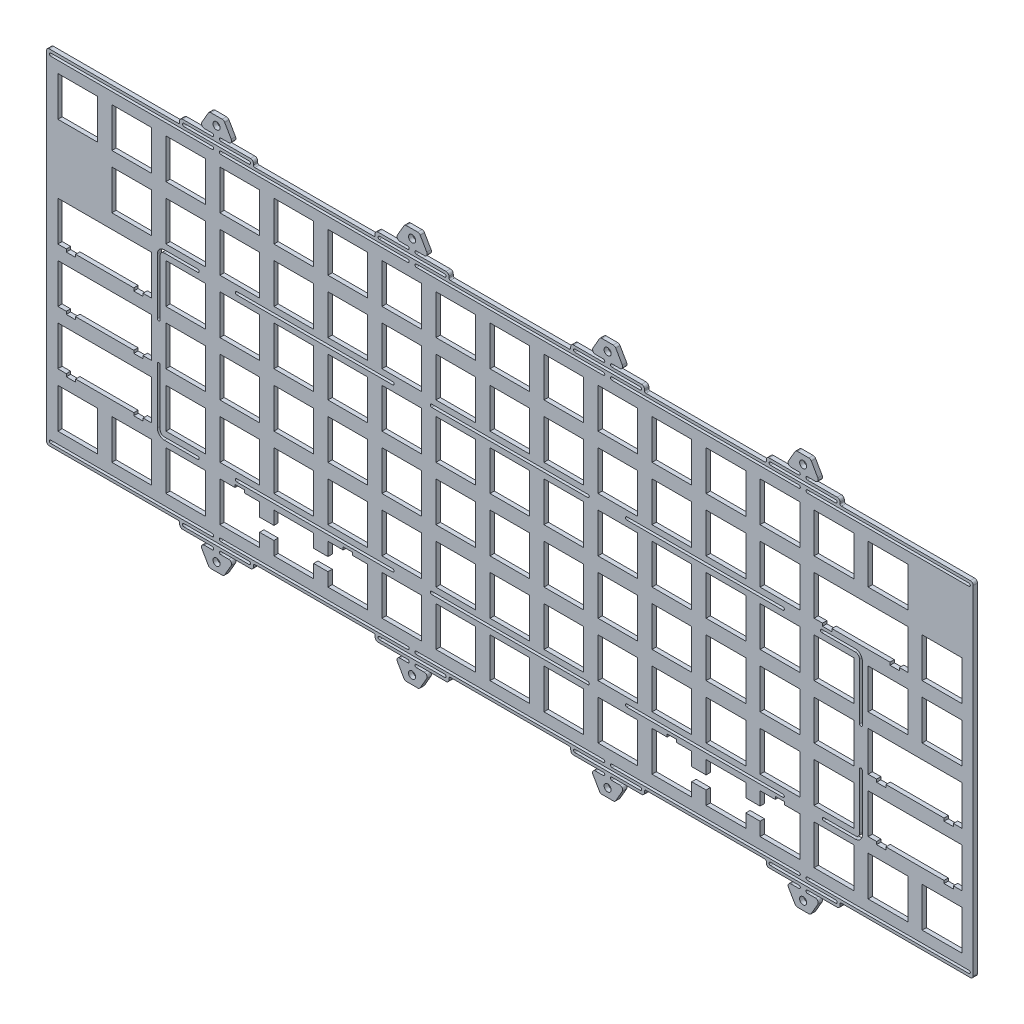
SolidWorks part; units mm, degrees
material "Acrylic (Medium-high impact)"
ref_plane "Front Plane" through (0, 0, 0) normal (0, 0, 1) x (1, 0, 0)
ref_plane "Top Plane" through (0, 0, 0) normal (0, 1, 0) x (1, 0, 0)
ref_plane "Right Plane" through (0, 0, 0) normal (1, 0, 0) x (0, 0, -1)
sketch "Sketch2" plane through (0, 0, 0) normal (0, 0, 1) x (1, 0, 0)
  line L0 (102.249, -54.6242) -> (102.249, -40.6233)
  line L1 (102.249, -40.6233) -> (96.9, -40.6233)
  line L2 (96.9, -40.6233) -> (96.9, -39.6546)
  line L3 (96.9, -39.6546) -> (93.6, -39.6546)
  line L4 (93.6, -39.6546) -> (93.6, -40.6233)
  line L5 (93.6, -40.6233) -> (88.25, -40.6233)
  line L6 (88.25, -40.6233) -> (88.25, -45.3238)
  line L7 (88.25, -45.3238) -> (83.199, -45.3238)
  line L8 (83.199, -45.3238) -> (83.199, -40.6233)
  line L9 (83.199, -40.6233) -> (69.2, -40.6233)
  line L10 (69.2, -40.6233) -> (69.2, -45.3238)
  line L11 (69.2, -45.3238) -> (64.149, -45.3238)
  line L12 (64.149, -45.3238) -> (64.149, -40.6233)
  line L13 (64.149, -40.6233) -> (58.801, -40.6233)
  line L14 (58.801, -40.6233) -> (58.801, -39.6546)
  line L15 (58.801, -39.6546) -> (55.5, -39.6546)
  line L16 (55.5, -39.6546) -> (55.5, -40.6233)
  line L17 (55.5, -40.6233) -> (50.15, -40.6233)
  line L18 (50.15, -40.6233) -> (50.15, -54.6242)
  line L19 (50.15, -54.6242) -> (64.149, -54.6242)
  line L20 (64.149, -54.6242) -> (64.149, -49.9223)
  line L21 (64.149, -49.9223) -> (69.2, -49.9223)
  line L22 (69.2, -49.9223) -> (69.2, -54.6242)
  line L23 (69.2, -54.6242) -> (83.199, -54.6242)
  line L24 (83.199, -54.6242) -> (83.199, -49.9223)
  line L25 (83.199, -49.9223) -> (88.25, -49.9223)
  line L26 (88.25, -49.9223) -> (88.25, -54.6242)
  line L27 (88.25, -54.6242) -> (102.249, -54.6242)
  line L28 (-50.1496, -54.6242) -> (-50.1496, -40.6233)
  line L29 (-50.1496, -40.6233) -> (-55.4991, -40.6233)
  line L30 (-55.4991, -40.6233) -> (-55.4991, -39.6546)
  line L31 (-55.4991, -39.6546) -> (-58.7994, -39.6546)
  line L32 (-58.7994, -39.6546) -> (-58.7994, -40.6233)
  line L33 (-58.7994, -40.6233) -> (-64.1503, -40.6233)
  line L34 (-64.1503, -40.6233) -> (-64.1503, -45.3238)
  line L35 (-64.1503, -45.3238) -> (-69.201, -45.3238)
  line L36 (-69.201, -45.3238) -> (-69.201, -40.6233)
  line L37 (-69.201, -40.6233) -> (-83.2003, -40.6233)
  line L38 (-83.2003, -40.6233) -> (-83.2003, -45.3238)
  line L39 (-83.2003, -45.3238) -> (-88.2496, -45.3238)
  line L40 (-88.2496, -45.3238) -> (-88.2496, -40.6233)
  line L41 (-88.2496, -40.6233) -> (-93.6003, -40.6233)
  line L42 (-93.6003, -40.6233) -> (-93.6003, -39.6546)
  line L43 (-93.6003, -39.6546) -> (-96.9003, -39.6546)
  line L44 (-96.9003, -39.6546) -> (-96.9003, -40.6233)
  line L45 (-96.9003, -40.6233) -> (-102.2503, -40.6233)
  line L46 (-102.2503, -40.6233) -> (-102.2503, -54.6242)
  line L47 (-102.2503, -54.6242) -> (-88.2496, -54.6242)
  line L48 (-88.2496, -54.6242) -> (-88.2496, -49.9223)
  line L49 (-88.2496, -49.9223) -> (-83.2003, -49.9223)
  line L50 (-83.2003, -49.9223) -> (-83.2003, -54.6242)
  line L51 (-83.2003, -54.6242) -> (-69.201, -54.6242)
  line L52 (-69.201, -54.6242) -> (-69.201, -49.9223)
  line L53 (-69.201, -49.9223) -> (-64.1503, -49.9223)
  line L54 (-64.1503, -49.9223) -> (-64.1503, -54.6242)
  line L55 (-64.1503, -54.6242) -> (-50.1496, -54.6242)
  line L56 (145.4, -40.6233) -> (159.399, -40.6233)
  line L57 (159.399, -40.6233) -> (159.399, -54.6242)
  line L58 (159.399, -54.6242) -> (145.4, -54.6242)
  line L59 (145.4, -54.6242) -> (145.4, -40.6233)
  line L60 (126.35, -40.6233) -> (140.349, -40.6233)
  line L61 (140.349, -40.6233) -> (140.349, -54.6242)
  line L62 (140.349, -54.6242) -> (126.35, -54.6242)
  line L63 (126.35, -54.6242) -> (126.35, -40.6233)
  line L64 (107.3, -40.6233) -> (121.299, -40.6233)
  line L65 (121.299, -40.6233) -> (121.299, -54.6242)
  line L66 (121.299, -54.6242) -> (107.3, -54.6242)
  line L67 (107.3, -54.6242) -> (107.3, -40.6233)
  line L68 (31.1, -40.6233) -> (45.099, -40.6233)
  line L69 (45.099, -40.6233) -> (45.099, -54.6242)
  line L70 (45.099, -54.6242) -> (31.1, -54.6242)
  line L71 (31.1, -54.6242) -> (31.1, -40.6233)
  line L72 (12.05, -40.6233) -> (26.049, -40.6233)
  line L73 (26.049, -40.6233) -> (26.049, -54.6242)
  line L74 (26.049, -54.6242) -> (12.05, -54.6242)
  line L75 (12.05, -54.6242) -> (12.05, -40.6233)
  line L76 (-7, -40.6233) -> (6.999, -40.6233)
  line L77 (6.999, -40.6233) -> (6.999, -54.6242)
  line L78 (6.999, -54.6242) -> (-7, -54.6242)
  line L79 (-7, -54.6242) -> (-7, -40.6233)
  line L80 (-26.05, -40.6233) -> (-12.051, -40.6233)
  line L81 (-12.051, -40.6233) -> (-12.051, -54.6242)
  line L82 (-12.051, -54.6242) -> (-26.05, -54.6242)
  line L83 (-26.05, -54.6242) -> (-26.05, -40.6233)
  line L84 (-45.102, -40.6233) -> (-31.101, -40.6233)
  line L85 (-31.101, -40.6233) -> (-31.101, -54.6242)
  line L86 (-31.101, -54.6242) -> (-45.102, -54.6242)
  line L87 (-45.102, -54.6242) -> (-45.102, -40.6233)
  line L88 (-121.3003, -40.6233) -> (-107.301, -40.6233)
  line L89 (-107.301, -40.6233) -> (-107.301, -54.6242)
  line L90 (-107.301, -54.6242) -> (-121.3003, -54.6242)
  line L91 (-121.3003, -54.6242) -> (-121.3003, -40.6233)
  line L92 (-140.3503, -40.6233) -> (-126.351, -40.6233)
  line L93 (-126.351, -40.6233) -> (-126.351, -54.6242)
  line L94 (-126.351, -54.6242) -> (-140.3503, -54.6242)
  line L95 (-140.3503, -54.6242) -> (-140.3503, -40.6233)
  line L96 (-159.4004, -40.6233) -> (-145.4008, -40.6233)
  line L97 (-145.4008, -40.6233) -> (-145.4008, -54.6242)
  line L98 (-145.4008, -54.6242) -> (-159.4004, -54.6242)
  line L99 (-159.4004, -54.6242) -> (-159.4004, -40.6233)
  line L100 (126.35, -21.5748) -> (126.35, -35.5742)
  line L101 (126.35, -35.5742) -> (129.325, -35.5742)
  line L102 (129.325, -35.5742) -> (129.325, -36.5443)
  line L103 (129.325, -36.5443) -> (132.624, -36.5443)
  line L104 (132.624, -36.5443) -> (132.624, -35.5742)
  line L105 (132.624, -35.5742) -> (153.125, -35.5742)
  line L106 (153.125, -35.5742) -> (153.125, -36.5443)
  line L107 (153.125, -36.5443) -> (156.424, -36.5443)
  line L108 (156.424, -36.5443) -> (156.424, -35.5742)
  line L109 (156.424, -35.5742) -> (159.399, -35.5742)
  line L110 (159.399, -35.5742) -> (159.399, -21.5748)
  line L111 (159.399, -21.5748) -> (126.35, -21.5748)
  line L112 (-159.4004, -21.5748) -> (-159.4004, -35.5742)
  line L113 (-159.4004, -35.5742) -> (-156.4252, -35.5742)
  line L114 (-156.4252, -35.5742) -> (-156.4252, -36.5443)
  line L115 (-156.4252, -36.5443) -> (-153.1262, -36.5443)
  line L116 (-153.1262, -36.5443) -> (-153.1262, -35.5742)
  line L117 (-153.1262, -35.5742) -> (-132.6251, -35.5742)
  line L118 (-132.6251, -35.5742) -> (-132.6251, -36.5443)
  line L119 (-132.6251, -36.5443) -> (-129.326, -36.5443)
  line L120 (-129.326, -36.5443) -> (-129.326, -35.5742)
  line L121 (-129.326, -35.5742) -> (-126.351, -35.5742)
  line L122 (-126.351, -35.5742) -> (-126.351, -21.5748)
  line L123 (-126.351, -21.5748) -> (-159.4004, -21.5748)
  line L124 (107.3, -21.5748) -> (121.299, -21.5748)
  line L125 (121.299, -21.5748) -> (121.299, -35.5742)
  line L126 (121.299, -35.5742) -> (107.3, -35.5742)
  line L127 (107.3, -35.5742) -> (107.3, -21.5748)
  line L128 (88.25, -21.5748) -> (102.249, -21.5748)
  line L129 (102.249, -21.5748) -> (102.249, -35.5742)
  line L130 (102.249, -35.5742) -> (88.25, -35.5742)
  line L131 (88.25, -35.5742) -> (88.25, -21.5748)
  line L132 (69.2, -21.5748) -> (83.199, -21.5748)
  line L133 (83.199, -21.5748) -> (83.199, -35.5742)
  line L134 (83.199, -35.5742) -> (69.2, -35.5742)
  line L135 (69.2, -35.5742) -> (69.2, -21.5748)
  line L136 (50.15, -21.5748) -> (64.149, -21.5748)
  line L137 (64.149, -21.5748) -> (64.149, -35.5742)
  line L138 (64.149, -35.5742) -> (50.15, -35.5742)
  line L139 (50.15, -35.5742) -> (50.15, -21.5748)
  line L140 (31.1, -21.5748) -> (45.099, -21.5748)
  line L141 (45.099, -21.5748) -> (45.099, -35.5742)
  line L142 (45.099, -35.5742) -> (31.1, -35.5742)
  line L143 (31.1, -35.5742) -> (31.1, -21.5748)
  line L144 (12.05, -21.5748) -> (26.049, -21.5748)
  line L145 (26.049, -21.5748) -> (26.049, -35.5742)
  line L146 (26.049, -35.5742) -> (12.05, -35.5742)
  line L147 (12.05, -35.5742) -> (12.05, -21.5748)
  line L148 (-7, -21.5748) -> (6.999, -21.5748)
  line L149 (6.999, -21.5748) -> (6.999, -35.5742)
  line L150 (6.999, -35.5742) -> (-7, -35.5742)
  line L151 (-7, -35.5742) -> (-7, -21.5748)
  line L152 (-26.05, -21.5748) -> (-12.051, -21.5748)
  line L153 (-12.051, -21.5748) -> (-12.051, -35.5742)
  line L154 (-12.051, -35.5742) -> (-26.05, -35.5742)
  line L155 (-26.05, -35.5742) -> (-26.05, -21.5748)
  line L156 (-45.102, -21.5748) -> (-31.101, -21.5748)
  line L157 (-31.101, -21.5748) -> (-31.101, -35.5742)
  line L158 (-31.101, -35.5742) -> (-45.102, -35.5742)
  line L159 (-45.102, -35.5742) -> (-45.102, -21.5748)
  line L160 (-64.1517, -21.5748) -> (-50.151, -21.5748)
  line L161 (-50.151, -21.5748) -> (-50.151, -35.5742)
  line L162 (-50.151, -35.5742) -> (-64.1517, -35.5742)
  line L163 (-64.1517, -35.5742) -> (-64.1517, -21.5748)
  line L164 (-83.2003, -21.5748) -> (-69.201, -21.5748)
  line L165 (-69.201, -21.5748) -> (-69.201, -35.5742)
  line L166 (-69.201, -35.5742) -> (-83.2003, -35.5742)
  line L167 (-83.2003, -35.5742) -> (-83.2003, -21.5748)
  line L168 (-102.2503, -21.5748) -> (-88.251, -21.5748)
  line L169 (-88.251, -21.5748) -> (-88.251, -35.5742)
  line L170 (-88.251, -35.5742) -> (-102.2503, -35.5742)
  line L171 (-102.2503, -35.5742) -> (-102.2503, -21.5748)
  line L172 (-121.3003, -21.5748) -> (-107.301, -21.5748)
  line L173 (-107.301, -21.5748) -> (-107.301, -35.5742)
  line L174 (-107.301, -35.5742) -> (-121.3003, -35.5742)
  line L175 (-121.3003, -35.5742) -> (-121.3003, -21.5748)
  line L176 (126.35, -2.5247) -> (126.35, -16.524)
  line L177 (126.35, -16.524) -> (129.325, -16.524)
  line L178 (129.325, -16.524) -> (129.325, -17.4942)
  line L179 (129.325, -17.4942) -> (132.624, -17.4942)
  line L180 (132.624, -17.4942) -> (132.624, -16.524)
  line L181 (132.624, -16.524) -> (153.125, -16.524)
  line L182 (153.125, -16.524) -> (153.125, -17.4942)
  line L183 (153.125, -17.4942) -> (156.424, -17.4942)
  line L184 (156.424, -17.4942) -> (156.424, -16.524)
  line L185 (156.424, -16.524) -> (159.399, -16.524)
  line L186 (159.399, -16.524) -> (159.399, -2.5247)
  line L187 (159.399, -2.5247) -> (126.35, -2.5247)
  line L188 (-159.4004, -2.5247) -> (-159.4004, -16.524)
  line L189 (-159.4004, -16.524) -> (-156.4252, -16.524)
  line L190 (-156.4252, -16.524) -> (-156.4252, -17.4942)
  line L191 (-156.4252, -17.4942) -> (-153.1262, -17.4942)
  line L192 (-153.1262, -17.4942) -> (-153.1262, -16.524)
  line L193 (-153.1262, -16.524) -> (-132.6251, -16.524)
  line L194 (-132.6251, -16.524) -> (-132.6251, -17.4942)
  line L195 (-132.6251, -17.4942) -> (-129.326, -17.4942)
  line L196 (-129.326, -17.4942) -> (-129.326, -16.524)
  line L197 (-129.326, -16.524) -> (-126.351, -16.524)
  line L198 (-126.351, -16.524) -> (-126.351, -2.5247)
  line L199 (-126.351, -2.5247) -> (-159.4004, -2.5247)
  line L200 (107.3, -2.5247) -> (121.299, -2.5247)
  line L201 (121.299, -2.5247) -> (121.299, -16.524)
  line L202 (121.299, -16.524) -> (107.3, -16.524)
  line L203 (107.3, -16.524) -> (107.3, -2.5247)
  line L204 (88.25, -2.5247) -> (102.249, -2.5247)
  line L205 (102.249, -2.5247) -> (102.249, -16.524)
  line L206 (102.249, -16.524) -> (88.25, -16.524)
  line L207 (88.25, -16.524) -> (88.25, -2.5247)
  line L208 (69.2, -2.5247) -> (83.199, -2.5247)
  line L209 (83.199, -2.5247) -> (83.199, -16.524)
  line L210 (83.199, -16.524) -> (69.2, -16.524)
  line L211 (69.2, -16.524) -> (69.2, -2.5247)
  line L212 (50.15, -2.5247) -> (64.149, -2.5247)
  line L213 (64.149, -2.5247) -> (64.149, -16.524)
  line L214 (64.149, -16.524) -> (50.15, -16.524)
  line L215 (50.15, -16.524) -> (50.15, -2.5247)
  line L216 (31.1, -2.5247) -> (45.099, -2.5247)
  line L217 (45.099, -2.5247) -> (45.099, -16.524)
  line L218 (45.099, -16.524) -> (31.1, -16.524)
  line L219 (31.1, -16.524) -> (31.1, -2.5247)
  line L220 (12.05, -2.5247) -> (26.049, -2.5247)
  line L221 (26.049, -2.5247) -> (26.049, -16.524)
  line L222 (26.049, -16.524) -> (12.05, -16.524)
  line L223 (12.05, -16.524) -> (12.05, -2.5247)
  line L224 (-7, -2.5247) -> (6.999, -2.5247)
  line L225 (6.999, -2.5247) -> (6.999, -16.524)
  line L226 (6.999, -16.524) -> (-7, -16.524)
  line L227 (-7, -16.524) -> (-7, -2.5247)
  line L228 (-26.05, -2.5247) -> (-12.051, -2.5247)
  line L229 (-12.051, -2.5247) -> (-12.051, -16.524)
  line L230 (-12.051, -16.524) -> (-26.05, -16.524)
  line L231 (-26.05, -16.524) -> (-26.05, -2.5247)
  line L232 (-45.102, -2.5247) -> (-31.101, -2.5247)
  line L233 (-31.101, -2.5247) -> (-31.101, -16.524)
  line L234 (-31.101, -16.524) -> (-45.102, -16.524)
  line L235 (-45.102, -16.524) -> (-45.102, -2.5247)
  line L236 (-64.1517, -2.5247) -> (-50.151, -2.5247)
  line L237 (-50.151, -2.5247) -> (-50.151, -16.524)
  line L238 (-50.151, -16.524) -> (-64.1517, -16.524)
  line L239 (-64.1517, -16.524) -> (-64.1517, -2.5247)
  line L240 (-83.2003, -2.5247) -> (-69.201, -2.5247)
  line L241 (-69.201, -2.5247) -> (-69.201, -16.524)
  line L242 (-69.201, -16.524) -> (-83.2003, -16.524)
  line L243 (-83.2003, -16.524) -> (-83.2003, -2.5247)
  line L244 (-102.2503, -2.5247) -> (-88.251, -2.5247)
  line L245 (-88.251, -2.5247) -> (-88.251, -16.524)
  line L246 (-88.251, -16.524) -> (-102.2503, -16.524)
  line L247 (-102.2503, -16.524) -> (-102.2503, -2.5247)
  line L248 (-121.3003, -2.5247) -> (-107.301, -2.5247)
  line L249 (-107.301, -2.5247) -> (-107.301, -16.524)
  line L250 (-107.301, -16.524) -> (-121.3003, -16.524)
  line L251 (-121.3003, -16.524) -> (-121.3003, -2.5247)
  line L252 (-159.4004, 16.5253) -> (-159.4004, 2.526)
  line L253 (-159.4004, 2.526) -> (-156.4252, 2.526)
  line L254 (-156.4252, 2.526) -> (-156.4252, 1.5558)
  line L255 (-156.4252, 1.5558) -> (-153.1262, 1.5558)
  line L256 (-153.1262, 1.5558) -> (-153.1262, 2.526)
  line L257 (-153.1262, 2.526) -> (-132.6251, 2.526)
  line L258 (-132.6251, 2.526) -> (-132.6251, 1.5558)
  line L259 (-132.6251, 1.5558) -> (-129.326, 1.5558)
  line L260 (-129.326, 1.5558) -> (-129.326, 2.526)
  line L261 (-129.326, 2.526) -> (-126.351, 2.526)
  line L262 (-126.351, 2.526) -> (-126.351, 16.5253)
  line L263 (-126.351, 16.5253) -> (-159.4004, 16.5253)
  line L264 (145.4, 16.5253) -> (159.399, 16.5253)
  line L265 (159.399, 16.5253) -> (159.399, 2.526)
  line L266 (159.399, 2.526) -> (145.4, 2.526)
  line L267 (145.4, 2.526) -> (145.4, 16.5253)
  line L268 (126.35, 16.5253) -> (140.349, 16.5253)
  line L269 (140.349, 16.5253) -> (140.349, 2.526)
  line L270 (140.349, 2.526) -> (126.35, 2.526)
  line L271 (126.35, 2.526) -> (126.35, 16.5253)
  line L272 (107.3, 16.5253) -> (121.299, 16.5253)
  line L273 (121.299, 16.5253) -> (121.299, 2.526)
  line L274 (121.299, 2.526) -> (107.3, 2.526)
  line L275 (107.3, 2.526) -> (107.3, 16.5253)
  line L276 (88.25, 16.5253) -> (102.249, 16.5253)
  line L277 (102.249, 16.5253) -> (102.249, 2.526)
  line L278 (102.249, 2.526) -> (88.25, 2.526)
  line L279 (88.25, 2.526) -> (88.25, 16.5253)
  line L280 (69.2, 16.5253) -> (83.199, 16.5253)
  line L281 (83.199, 16.5253) -> (83.199, 2.526)
  line L282 (83.199, 2.526) -> (69.2, 2.526)
  line L283 (69.2, 2.526) -> (69.2, 16.5253)
  line L284 (50.15, 16.5253) -> (64.149, 16.5253)
  line L285 (64.149, 16.5253) -> (64.149, 2.526)
  line L286 (64.149, 2.526) -> (50.15, 2.526)
  line L287 (50.15, 2.526) -> (50.15, 16.5253)
  line L288 (31.1, 16.5253) -> (45.099, 16.5253)
  line L289 (45.099, 16.5253) -> (45.099, 2.526)
  line L290 (45.099, 2.526) -> (31.1, 2.526)
  line L291 (31.1, 2.526) -> (31.1, 16.5253)
  line L292 (12.05, 16.5253) -> (26.049, 16.5253)
  line L293 (26.049, 16.5253) -> (26.049, 2.526)
  line L294 (26.049, 2.526) -> (12.05, 2.526)
  line L295 (12.05, 2.526) -> (12.05, 16.5253)
  line L296 (-7, 16.5253) -> (6.999, 16.5253)
  line L297 (6.999, 16.5253) -> (6.999, 2.526)
  line L298 (6.999, 2.526) -> (-7, 2.526)
  line L299 (-7, 2.526) -> (-7, 16.5253)
  line L300 (-26.05, 16.5253) -> (-12.051, 16.5253)
  line L301 (-12.051, 16.5253) -> (-12.051, 2.526)
  line L302 (-12.051, 2.526) -> (-26.05, 2.526)
  line L303 (-26.05, 2.526) -> (-26.05, 16.5253)
  line L304 (-45.102, 16.5253) -> (-31.101, 16.5253)
  line L305 (-31.101, 16.5253) -> (-31.101, 2.526)
  line L306 (-31.101, 2.526) -> (-45.102, 2.526)
  line L307 (-45.102, 2.526) -> (-45.102, 16.5253)
  line L308 (-64.1517, 16.5253) -> (-50.151, 16.5253)
  line L309 (-50.151, 16.5253) -> (-50.151, 2.526)
  line L310 (-50.151, 2.526) -> (-64.1517, 2.526)
  line L311 (-64.1517, 2.526) -> (-64.1517, 16.5253)
  line L312 (-83.2003, 16.5253) -> (-69.201, 16.5253)
  line L313 (-69.201, 16.5253) -> (-69.201, 2.526)
  line L314 (-69.201, 2.526) -> (-83.2003, 2.526)
  line L315 (-83.2003, 2.526) -> (-83.2003, 16.5253)
  line L316 (-102.2503, 16.5253) -> (-88.251, 16.5253)
  line L317 (-88.251, 16.5253) -> (-88.251, 2.526)
  line L318 (-88.251, 2.526) -> (-102.2503, 2.526)
  line L319 (-102.2503, 2.526) -> (-102.2503, 16.5253)
  line L320 (-121.3003, 16.5253) -> (-107.301, 16.5253)
  line L321 (-107.301, 16.5253) -> (-107.301, 2.526)
  line L322 (-107.301, 2.526) -> (-121.3003, 2.526)
  line L323 (-121.3003, 2.526) -> (-121.3003, 16.5253)
  line L324 (107.3, 35.5753) -> (107.3, 21.576)
  line L325 (107.3, 21.576) -> (110.275, 21.576)
  line L326 (110.275, 21.576) -> (110.275, 20.6058)
  line L327 (110.275, 20.6058) -> (113.574, 20.6058)
  line L328 (113.574, 20.6058) -> (113.574, 21.576)
  line L329 (113.574, 21.576) -> (134.075, 21.576)
  line L330 (134.075, 21.576) -> (134.075, 20.6058)
  line L331 (134.075, 20.6058) -> (137.374, 20.6058)
  line L332 (137.374, 20.6058) -> (137.374, 21.576)
  line L333 (137.374, 21.576) -> (140.349, 21.576)
  line L334 (140.349, 21.576) -> (140.349, 35.5753)
  line L335 (140.349, 35.5753) -> (107.3, 35.5753)
  line L336 (145.4, 35.5753) -> (159.399, 35.5753)
  line L337 (159.399, 35.5753) -> (159.399, 21.576)
  line L338 (159.399, 21.576) -> (145.4, 21.576)
  line L339 (145.4, 21.576) -> (145.4, 35.5753)
  line L340 (88.25, 35.5753) -> (102.249, 35.5753)
  line L341 (102.249, 35.5753) -> (102.249, 21.576)
  line L342 (102.249, 21.576) -> (88.25, 21.576)
  line L343 (88.25, 21.576) -> (88.25, 35.5753)
  line L344 (69.2, 35.5753) -> (83.199, 35.5753)
  line L345 (83.199, 35.5753) -> (83.199, 21.576)
  line L346 (83.199, 21.576) -> (69.2, 21.576)
  line L347 (69.2, 21.576) -> (69.2, 35.5753)
  line L348 (50.15, 35.5753) -> (64.149, 35.5753)
  line L349 (64.149, 35.5753) -> (64.149, 21.576)
  line L350 (64.149, 21.576) -> (50.15, 21.576)
  line L351 (50.15, 21.576) -> (50.15, 35.5753)
  line L352 (31.1, 35.5753) -> (45.099, 35.5753)
  line L353 (45.099, 35.5753) -> (45.099, 21.576)
  line L354 (45.099, 21.576) -> (31.1, 21.576)
  line L355 (31.1, 21.576) -> (31.1, 35.5753)
  line L356 (12.05, 35.5753) -> (26.049, 35.5753)
  line L357 (26.049, 35.5753) -> (26.049, 21.576)
  line L358 (26.049, 21.576) -> (12.05, 21.576)
  line L359 (12.05, 21.576) -> (12.05, 35.5753)
  line L360 (-7, 35.5753) -> (6.999, 35.5753)
  line L361 (6.999, 35.5753) -> (6.999, 21.576)
  line L362 (6.999, 21.576) -> (-7, 21.576)
  line L363 (-7, 21.576) -> (-7, 35.5753)
  line L364 (-26.05, 35.5753) -> (-12.051, 35.5753)
  line L365 (-12.051, 35.5753) -> (-12.051, 21.576)
  line L366 (-12.051, 21.576) -> (-26.05, 21.576)
  line L367 (-26.05, 21.576) -> (-26.05, 35.5753)
  line L368 (-45.102, 35.5753) -> (-31.101, 35.5753)
  line L369 (-31.101, 35.5753) -> (-31.101, 21.576)
  line L370 (-31.101, 21.576) -> (-45.102, 21.576)
  line L371 (-45.102, 21.576) -> (-45.102, 35.5753)
  line L372 (-64.1517, 35.5753) -> (-50.151, 35.5753)
  line L373 (-50.151, 35.5753) -> (-50.151, 21.576)
  line L374 (-50.151, 21.576) -> (-64.1517, 21.576)
  line L375 (-64.1517, 21.576) -> (-64.1517, 35.5753)
  line L376 (-83.2003, 35.5753) -> (-69.201, 35.5753)
  line L377 (-69.201, 35.5753) -> (-69.201, 21.576)
  line L378 (-69.201, 21.576) -> (-83.2003, 21.576)
  line L379 (-83.2003, 21.576) -> (-83.2003, 35.5753)
  line L380 (-102.2503, 35.5753) -> (-88.251, 35.5753)
  line L381 (-88.251, 35.5753) -> (-88.251, 21.576)
  line L382 (-88.251, 21.576) -> (-102.2503, 21.576)
  line L383 (-102.2503, 21.576) -> (-102.2503, 35.5753)
  line L384 (-121.3003, 35.5753) -> (-107.301, 35.5753)
  line L385 (-107.301, 35.5753) -> (-107.301, 21.576)
  line L386 (-107.301, 21.576) -> (-121.3003, 21.576)
  line L387 (-121.3003, 21.576) -> (-121.3003, 35.5753)
  line L388 (-140.3503, 35.5753) -> (-126.351, 35.5753)
  line L389 (-126.351, 35.5753) -> (-126.351, 21.576)
  line L390 (-126.351, 21.576) -> (-140.3503, 21.576)
  line L391 (-140.3503, 21.576) -> (-140.3503, 35.5753)
  line L392 (126.35, 54.6252) -> (140.349, 54.6252)
  line L393 (140.349, 54.6252) -> (140.349, 40.626)
  line L394 (140.349, 40.626) -> (126.35, 40.626)
  line L395 (126.35, 40.626) -> (126.35, 54.6252)
  line L396 (107.3, 54.6252) -> (121.299, 54.6252)
  line L397 (121.299, 54.6252) -> (121.299, 40.626)
  line L398 (121.299, 40.626) -> (107.3, 40.626)
  line L399 (107.3, 40.626) -> (107.3, 54.6252)
  line L400 (88.25, 54.6252) -> (102.249, 54.6252)
  line L401 (102.249, 54.6252) -> (102.249, 40.626)
  line L402 (102.249, 40.626) -> (88.25, 40.626)
  line L403 (88.25, 40.626) -> (88.25, 54.6252)
  line L404 (69.2, 54.6252) -> (83.199, 54.6252)
  line L405 (83.199, 54.6252) -> (83.199, 40.626)
  line L406 (83.199, 40.626) -> (69.2, 40.626)
  line L407 (69.2, 40.626) -> (69.2, 54.6252)
  line L408 (50.15, 54.6252) -> (64.149, 54.6252)
  line L409 (64.149, 54.6252) -> (64.149, 40.626)
  line L410 (64.149, 40.626) -> (50.15, 40.626)
  line L411 (50.15, 40.626) -> (50.15, 54.6252)
  line L412 (31.1, 54.6252) -> (45.099, 54.6252)
  line L413 (45.099, 54.6252) -> (45.099, 40.626)
  line L414 (45.099, 40.626) -> (31.1, 40.626)
  line L415 (31.1, 40.626) -> (31.1, 54.6252)
  line L416 (12.05, 54.6252) -> (26.049, 54.6252)
  line L417 (26.049, 54.6252) -> (26.049, 40.626)
  line L418 (26.049, 40.626) -> (12.05, 40.626)
  line L419 (12.05, 40.626) -> (12.05, 54.6252)
  line L420 (-7, 54.6252) -> (6.999, 54.6252)
  line L421 (6.999, 54.6252) -> (6.999, 40.626)
  line L422 (6.999, 40.626) -> (-7, 40.626)
  line L423 (-7, 40.626) -> (-7, 54.6252)
  line L424 (-26.05, 54.6252) -> (-12.051, 54.6252)
  line L425 (-12.051, 54.6252) -> (-12.051, 40.626)
  line L426 (-12.051, 40.626) -> (-26.05, 40.626)
  line L427 (-26.05, 40.626) -> (-26.05, 54.6252)
  line L428 (-45.102, 54.6252) -> (-31.101, 54.6252)
  line L429 (-31.101, 54.6252) -> (-31.101, 40.626)
  line L430 (-31.101, 40.626) -> (-45.102, 40.626)
  line L431 (-45.102, 40.626) -> (-45.102, 54.6252)
  line L432 (-64.1517, 54.6252) -> (-50.151, 54.6252)
  line L433 (-50.151, 54.6252) -> (-50.151, 40.626)
  line L434 (-50.151, 40.626) -> (-64.1517, 40.626)
  line L435 (-64.1517, 40.626) -> (-64.1517, 54.6252)
  line L436 (-83.2003, 54.6252) -> (-69.201, 54.6252)
  line L437 (-69.201, 54.6252) -> (-69.201, 40.626)
  line L438 (-69.201, 40.626) -> (-83.2003, 40.626)
  line L439 (-83.2003, 40.626) -> (-83.2003, 54.6252)
  line L440 (-102.2503, 54.6252) -> (-88.251, 54.6252)
  line L441 (-88.251, 54.6252) -> (-88.251, 40.626)
  line L442 (-88.251, 40.626) -> (-102.2503, 40.626)
  line L443 (-102.2503, 40.626) -> (-102.2503, 54.6252)
  line L444 (-121.3003, 54.6252) -> (-107.301, 54.6252)
  line L445 (-107.301, 54.6252) -> (-107.301, 40.626)
  line L446 (-107.301, 40.626) -> (-121.3003, 40.626)
  line L447 (-121.3003, 40.626) -> (-121.3003, 54.6252)
  line L448 (-140.3503, 54.6252) -> (-126.351, 54.6252)
  line L449 (-126.351, 54.6252) -> (-126.351, 40.626)
  line L450 (-126.351, 40.626) -> (-140.3503, 40.626)
  line L451 (-140.3503, 40.626) -> (-140.3503, 54.6252)
  line L452 (-159.4004, 54.6252) -> (-145.4008, 54.6252)
  line L453 (-145.4008, 54.6252) -> (-145.4008, 40.626)
  line L454 (-145.4008, 40.626) -> (-159.4004, 40.626)
  line L455 (-159.4004, 40.626) -> (-159.4004, 54.6252)
  line L456 (-162.4006, -55.6246) -> (-162.4006, 55.6256) construction
  line L457 (-160.4006, 57.6256) -> (160.3992, 57.6256) construction
  line L458 (162.3992, 55.6256) -> (162.3992, -55.6246) construction
  line L459 (160.3992, -57.6246) -> (-160.4006, -57.6246) construction
  line L461 (-172.4004, 69.6252) -> (172.399, 69.6252)
  line L462 (-172.4004, 69.6252) -> (-172.4004, -69.6242)
  line L463 (-172.4004, -69.6242) -> (172.399, -69.6242)
  line L464 (172.399, 69.6252) -> (172.399, -69.6242)
  circle A0 centre (-152.4006, 47.6256) radius 2 construction
  circle A1 centre (-133.3508, 47.6256) radius 2 construction
  circle A2 centre (-114.3008, 47.6256) radius 2 construction
  circle A3 centre (-95.2508, 47.6256) radius 2 construction
  circle A4 centre (-76.2008, 47.6256) radius 2 construction
  circle A5 centre (-57.1508, 47.6256) radius 2 construction
  circle A6 centre (-38.1008, 47.6256) radius 2 construction
  circle A7 centre (-19.0508, 47.6256) radius 2 construction
  circle A8 centre (-0.0008, 47.6256) radius 2 construction
  circle A9 centre (19.0492, 47.6256) radius 2 construction
  circle A10 centre (38.0992, 47.6256) radius 2 construction
  circle A11 centre (57.1492, 47.6256) radius 2 construction
  circle A12 centre (76.1992, 47.6256) radius 2 construction
  circle A13 centre (95.2492, 47.6256) radius 2 construction
  circle A14 centre (114.2992, 47.6256) radius 2 construction
  circle A15 centre (133.3492, 47.6256) radius 2 construction
  circle A16 centre (152.3992, 28.5756) radius 2 construction
  circle A17 centre (133.3492, 28.5756) radius 2 construction
  circle A18 centre (95.2492, 28.5756) radius 2 construction
  circle A19 centre (152.3992, 9.5256) radius 2 construction
  circle A20 centre (133.3492, 9.5256) radius 2 construction
  circle A21 centre (114.2992, 9.5256) radius 2 construction
  circle A22 centre (95.2492, 9.5256) radius 2 construction
  circle A23 centre (76.1992, 9.5256) radius 2 construction
  circle A24 centre (76.1992, 28.5756) radius 2 construction
  circle A25 centre (57.1492, 28.5756) radius 2 construction
  circle A26 centre (57.1492, 9.5256) radius 2 construction
  circle A27 centre (38.0992, 28.5756) radius 2 construction
  circle A28 centre (19.0492, 28.5756) radius 2 construction
  circle A29 centre (-0.0008, 28.5756) radius 2 construction
  circle A30 centre (-19.0508, 28.5756) radius 2 construction
  circle A31 centre (-38.1008, 28.5756) radius 2 construction
  circle A32 centre (-57.1508, 28.5756) radius 2 construction
  circle A33 centre (-76.2008, 28.5756) radius 2 construction
  circle A34 centre (-95.2508, 28.5756) radius 2 construction
  circle A35 centre (-114.3008, 28.5756) radius 2 construction
  circle A36 centre (-133.3508, 28.5756) radius 2 construction
  circle A37 centre (-133.3508, 9.5256) radius 2 construction
  circle A38 centre (-114.3008, 9.5256) radius 2 construction
  circle A39 centre (-133.3508, -9.5244) radius 2 construction
  circle A40 centre (-95.2508, 9.5256) radius 2 construction
  circle A41 centre (-76.2008, 9.5256) radius 2 construction
  circle A42 centre (-57.1508, 9.5256) radius 2 construction
  circle A43 centre (-38.1008, 9.5256) radius 2 construction
  circle A44 centre (-19.0508, 9.5256) radius 2 construction
  circle A45 centre (-0.0008, 9.5256) radius 2 construction
  circle A46 centre (19.0492, 9.5256) radius 2 construction
  circle A47 centre (38.0992, 9.5256) radius 2 construction
  circle A48 centre (152.3992, -9.5244) radius 2 construction
  circle A49 centre (152.3992, -28.5746) radius 2 construction
  circle A50 centre (152.3992, -47.6246) radius 2 construction
  circle A51 centre (133.3492, -47.6246) radius 2 construction
  circle A52 centre (114.2992, -47.6246) radius 2 construction
  circle A53 centre (95.2492, -47.6246) radius 2 construction
  circle A54 centre (114.2992, -28.5746) radius 2 construction
  circle A55 centre (95.2492, -28.5746) radius 2 construction
  circle A56 centre (76.1992, -47.6246) radius 2 construction
  circle A57 centre (57.1492, -47.6246) radius 2 construction
  circle A58 centre (57.1492, -28.5746) radius 2 construction
  circle A59 centre (57.1492, -9.5244) radius 2 construction
  circle A60 centre (76.1992, -9.5244) radius 2 construction
  circle A61 centre (76.1992, -28.5746) radius 2 construction
  circle A62 centre (95.2492, -9.5244) radius 2 construction
  circle A63 centre (114.2992, -9.5244) radius 2 construction
  circle A64 centre (38.0992, -9.5244) radius 2 construction
  circle A65 centre (38.0992, -28.5746) radius 2 construction
  circle A66 centre (38.0992, -47.6246) radius 2 construction
  circle A67 centre (19.0492, -28.5746) radius 2 construction
  circle A68 centre (19.0492, -9.5244) radius 2 construction
  circle A69 centre (19.0492, -47.6246) radius 2 construction
  circle A70 centre (-0.0008, -9.5244) radius 2 construction
  circle A71 centre (-19.0508, -9.5244) radius 2 construction
  circle A72 centre (-19.0508, -28.5746) radius 2 construction
  circle A73 centre (-0.0008, -28.5746) radius 2 construction
  circle A74 centre (-0.0008, -47.6246) radius 2 construction
  circle A75 centre (-19.0508, -47.6246) radius 2 construction
  circle A76 centre (-38.1008, -28.5746) radius 2 construction
  circle A77 centre (-38.1008, -9.5244) radius 2 construction
  circle A78 centre (-57.1508, -9.5244) radius 2 construction
  circle A79 centre (-38.1008, -47.6246) radius 2 construction
  circle A80 centre (-57.1494, -47.6246) radius 2 construction
  circle A81 centre (-57.1508, -28.5746) radius 2 construction
  circle A82 centre (-76.2008, -47.6246) radius 2 construction
  circle A83 centre (-76.2008, -28.5746) radius 2 construction
  circle A84 centre (-76.2008, -9.5244) radius 2 construction
  circle A85 centre (-95.2508, -9.5244) radius 2 construction
  circle A86 centre (-95.2508, -28.5746) radius 2 construction
  circle A87 centre (-95.2508, -47.6246) radius 2 construction
  circle A88 centre (-114.3008, -47.6246) radius 2 construction
  circle A89 centre (-114.3008, -28.5746) radius 2 construction
  circle A90 centre (-114.3008, -9.5244) radius 2 construction
  circle A91 centre (-133.3508, -28.5746) radius 2 construction
  circle A92 centre (-133.3508, -47.6246) radius 2 construction
  circle A93 centre (-152.4006, -47.6246) radius 2 construction
  circle A94 centre (-152.4006, 9.5256) radius 2 construction
  circle A95 centre (-152.4006, -9.5244) radius 2 construction
  circle A96 centre (-152.4006, -28.5746) radius 2 construction
  circle A97 centre (133.3497, -28.5746) radius 2 construction
  circle A98 centre (133.3497, -9.5244) radius 2 construction
  circle A99 centre (114.2997, 28.5756) radius 2 construction
  circle A100 centre (-142.8757, 9.5257) radius 2 construction
  circle A101 centre (-142.8757, -9.5243) radius 2 construction
  circle A102 centre (-142.8757, -28.5744) radius 2 construction
  circle A103 centre (142.8745, -28.5744) radius 2 construction
  circle A104 centre (142.8745, -9.5243) radius 2 construction
  circle A105 centre (123.8245, 28.5757) radius 2 construction
  arc A106 (-160.4006, 57.6256) -> (-162.4006, 55.6256) centre (-160.4006, 55.6256) ccw construction
  arc A107 (162.3992, 55.6256) -> (160.3992, 57.6256) centre (160.3992, 55.6256) ccw construction
  arc A108 (160.3992, -57.6246) -> (162.3992, -55.6246) centre (160.3992, -55.6246) ccw construction
  arc A109 (-162.4006, -55.6246) -> (-160.4006, -57.6246) centre (-160.4006, -55.6246) ccw construction
  point P680 (0, 0)
  dimension "D1" = 4
  dimension "D2" = 6.999
  dimension "D3" = 12.05
  dimension "D4" = 19.0492
  dimension "D5" = 26.049
  dimension "D6" = 31.1
  dimension "D7" = 38.0992
  dimension "D8" = 50.15
  dimension "D9" = 55.5
  dimension "D10" = 57.1492
  dimension "D11" = 58.801
  dimension "D12" = 69.2
  dimension "D13" = 76.1992
  dimension "D14" = 95.2492
  dimension "D15" = 96.9
  dimension "D16" = 107.3
  dimension "D17" = 110.275
  dimension "D18" = 113.574
  dimension "D19" = 114.2992
  dimension "D20" = 114.2997
  dimension "D21" = 123.8245
  dimension "D22" = 133.3492
  dimension "D23" = 133.3497
  dimension "D24" = 134.075
  dimension "D25" = 142.8745
  dimension "D26" = 152.3992
  dimension "D27" = 162.3992
  dimension "D28" = 0.0008
  dimension "D29" = 12.051
  dimension "D30" = 19.0508
  dimension "D31" = 31.101
  dimension "D32" = 38.1008
  dimension "D33" = 45.102
  dimension "D34" = 50.1496
  dimension "D35" = 50.151
  dimension "D36" = 55.4991
  dimension "D37" = 57.1494
  dimension "D38" = 57.1508
  dimension "D39" = 58.7994
  dimension "D40" = 64.1503
  dimension "D41" = 69.201
  dimension "D42" = 76.2008
  dimension "D43" = 83.2003
  dimension "D44" = 88.2496
  dimension "D45" = 95.2508
  dimension "D46" = 107.301
  dimension "D47" = 114.3008
  dimension "D48" = 126.351
  dimension "D49" = 132.6251
  dimension "D50" = 133.3508
  dimension "D51" = 142.8757
  dimension "D52" = 145.4008
  dimension "D53" = 152.4006
  dimension "D54" = 153.1262
  dimension "D55" = 159.4004
  dimension "D56" = 162.4006
  dimension "D57" = 1.5558
  dimension "D58" = 2.526
  dimension "D59" = 9.5256
  dimension "D60" = 9.5257
  dimension "D61" = 20.6058
  dimension "D62" = 28.5756
  dimension "D63" = 28.5757
  dimension "D64" = 40.626
  dimension "D65" = 47.6256
  dimension "D66" = 54.6252
  dimension "D67" = 57.6256
  dimension "D68" = 2.5247
  dimension "D69" = 9.5243
  dimension "D70" = 9.5244
  dimension "D71" = 21.5748
  dimension "D72" = 28.5744
  dimension "D73" = 28.5746
  dimension "D74" = 35.5742
  dimension "D75" = 39.6546
  dimension "D76" = 40.6233
  dimension "D77" = 45.3238
  dimension "D78" = 47.6246
  dimension "D79" = 49.9223
  dimension "D80" = 54.6242
  dimension "D81" = 57.6246
  dimension "D82" = 0.9701
  dimension "D83" = 172.399
  dimension "D84" = 69.6242
  dimension "D86" = 172.4004
  dimension "D87" = 69.6252
extrude "Boss-Extrude1" add sketch "Sketch2" along normal blind 1.524
sketch "Sketch3" plane through (0, 0, 1.524) normal (0, 0, 1) x (1, 0, 0)
  line L0 (-172.4004, -69.6242) -> (172.399, -69.6242) construction
  line L1 (-172.4004, -69.6242) -> (-103.4405, -69.6242) construction
  line L2 (-114.9405, -61.6242) -> (-91.9405, -61.6242)
  line L3 (-34.4807, -69.6242) -> (34.4792, -69.6242) construction
  line L4 (34.4792, -69.6242) -> (103.4391, -69.6242) construction
  line L5 (103.4391, -69.6242) -> (172.399, -69.6242) construction
  line L6 (-103.4405, -69.6242) -> (-103.4405, 85.065) construction
  line L7 (-34.4807, -69.6242) -> (-34.4807, 85.065) construction
  line L8 (34.4792, -69.6242) -> (34.4792, 85.065) construction
  line L9 (103.4391, -69.6242) -> (103.4391, 85.065) construction
  line L10 (-114.9405, -60.6242) -> (-91.9405, -60.6242)
  line L11 (-106.3065, -69.1242) -> (-108.6159, -65.1242)
  line L12 (-107.7499, -63.6242) -> (-104.9405, -63.6242)
  line L13 (-104.9405, -62.6242) -> (-115.4405, -62.6242)
  line L14 (-116.4405, -61.6242) -> (-116.4405, -61.1242)
  line L15 (-116.9405, -60.6242) -> (-137.9205, -60.6242)
  line L16 (-103.4405, -69.6242) -> (-34.4807, -69.6242) construction
  line L17 (-103.4405, -55.7341) -> (-172.4004, -55.7341) construction
  line L18 (-172.4004, 69.6252) -> (-172.4004, -69.6242) construction
  line L19 (-137.9205, -55.7341) -> (-137.9205, -69.6242) construction
  line L20 (-116.4405, -60.6242) -> (-137.9205, -60.6242) construction
  line L21 (-34.4807, -56.8321) -> (34.4792, -56.8321) construction
  line L25 (-103.4405, -60.6242) -> (-103.4405, -61.6242) construction
  line L26 (-105.4405, -69.6242) -> (-101.4405, -69.6242)
  line L27 (-100.5745, -69.1242) -> (-98.2651, -65.1242)
  line L28 (-99.1311, -63.6242) -> (-101.9405, -63.6242)
  line L29 (-101.9405, -62.6242) -> (-91.4405, -62.6242)
  line L30 (-90.4405, -61.6242) -> (-90.4405, -61.1242)
  line L31 (-89.9405, -60.6242) -> (-68.9606, -60.6242)
  line L32 (-47.9806, -60.6242) -> (-68.9606, -60.6242)
  line L33 (-47.4807, -61.6242) -> (-47.4807, -61.1242)
  line L34 (-35.9807, -62.6242) -> (-46.4807, -62.6242)
  line L35 (-45.9807, -61.6242) -> (-22.9807, -61.6242)
  line L36 (-38.7901, -63.6242) -> (-35.9807, -63.6242)
  line L37 (-37.3467, -69.1242) -> (-39.6561, -65.1242)
  line L38 (-36.4807, -69.6242) -> (-32.4807, -69.6242)
  line L39 (-31.6146, -69.1242) -> (-29.3052, -65.1242)
  line L40 (-30.1713, -63.6242) -> (-32.9807, -63.6242)
  line L41 (-32.9807, -62.6242) -> (-22.4807, -62.6242)
  line L42 (-21.4807, -61.6242) -> (-21.4807, -61.1242)
  line L43 (-20.9807, -60.6242) -> (-0.0007, -60.6242)
  line L44 (20.9792, -60.6242) -> (-0.0007, -60.6242)
  line L45 (21.4792, -61.6242) -> (21.4792, -61.1242)
  line L46 (32.9792, -62.6242) -> (22.4792, -62.6242)
  line L47 (22.9792, -61.6242) -> (45.9792, -61.6242)
  line L48 (30.1698, -63.6242) -> (32.9792, -63.6242)
  line L49 (31.6132, -69.1242) -> (29.3038, -65.1242)
  line L50 (32.4792, -69.6242) -> (36.4792, -69.6242)
  line L51 (37.3452, -69.1242) -> (39.6546, -65.1242)
  line L52 (38.7886, -63.6242) -> (35.9792, -63.6242)
  line L53 (35.9792, -62.6242) -> (46.4792, -62.6242)
  line L54 (47.4792, -61.6242) -> (47.4792, -61.1242)
  line L55 (47.9792, -60.6242) -> (68.9592, -60.6242)
  line L56 (89.9391, -60.6242) -> (68.9592, -60.6242)
  line L57 (90.4391, -61.6242) -> (90.4391, -61.1242)
  line L58 (101.9391, -62.6242) -> (91.4391, -62.6242)
  line L59 (91.9391, -61.6242) -> (114.9391, -61.6242)
  line L60 (99.1297, -63.6242) -> (101.9391, -63.6242)
  line L61 (100.5731, -69.1242) -> (98.2637, -65.1242)
  line L62 (101.4391, -69.6242) -> (105.4391, -69.6242)
  line L63 (106.3051, -69.1242) -> (108.6145, -65.1242)
  line L64 (107.7485, -63.6242) -> (104.9391, -63.6242)
  line L65 (104.9391, -62.6242) -> (115.4391, -62.6242)
  line L66 (116.4391, -61.6242) -> (116.4391, -61.1242)
  line L67 (116.9391, -60.6242) -> (137.919, -60.6242)
  line L68 (0, 0) -> (-214.8315, 0) construction
  line L69 (-45.9807, -60.6242) -> (-22.9807, -60.6242)
  line L70 (22.9792, -60.6242) -> (45.9792, -60.6242)
  line L71 (91.9391, -60.6242) -> (114.9391, -60.6242)
  line L72 (-137.9205, -60.6242) -> (-162.4004, -60.6242)
  line L73 (-0.0007, -69.6242) -> (-0.0007, 88.9307) construction
  line L74 (-152.7669, -60.6242) -> (-152.7669, -69.6242) construction
  line L75 (-163.4004, -47.018) -> (-172.4004, -47.018) construction
  line L76 (163.399, -59.6242) -> (163.399, 59.6242)
  line L77 (137.919, -60.6242) -> (162.399, -60.6242)
  line L78 (-163.4004, 47.018) -> (-172.4004, 47.018) construction
  line L79 (-163.4004, -59.6242) -> (-163.4004, 59.6242)
  line L80 (-152.7669, 60.6242) -> (-152.7669, 69.6242) construction
  line L81 (-103.4405, 60.6242) -> (-103.4405, 61.6242) construction
  line L82 (-34.4807, 56.8321) -> (34.4792, 56.8321) construction
  line L83 (-116.4405, 60.6242) -> (-137.9205, 60.6242) construction
  line L84 (-137.9205, 55.7341) -> (-137.9205, 69.6242) construction
  line L85 (-103.4405, 55.7341) -> (-172.4004, 55.7341) construction
  line L86 (-103.4405, 69.6242) -> (-34.4807, 69.6242) construction
  line L87 (34.4792, 69.6242) -> (103.4391, 69.6242) construction
  line L88 (-34.4807, 69.6242) -> (34.4792, 69.6242) construction
  line L89 (-172.4004, 69.6242) -> (-103.4405, 69.6242) construction
  line L90 (137.919, 60.6242) -> (162.399, 60.6242)
  line L91 (-137.9205, 60.6242) -> (-162.4004, 60.6242)
  line L92 (91.9391, 60.6242) -> (114.9391, 60.6242)
  line L93 (22.9792, 60.6242) -> (45.9792, 60.6242)
  line L94 (-45.9807, 60.6242) -> (-22.9807, 60.6242)
  line L95 (116.9391, 60.6242) -> (137.919, 60.6242)
  line L96 (116.4391, 61.6242) -> (116.4391, 61.1242)
  line L97 (104.9391, 62.6242) -> (115.4391, 62.6242)
  line L98 (107.7485, 63.6242) -> (104.9391, 63.6242)
  line L99 (106.3051, 69.1242) -> (108.6145, 65.1242)
  line L100 (101.4391, 69.6242) -> (105.4391, 69.6242)
  line L101 (100.5731, 69.1242) -> (98.2637, 65.1242)
  line L102 (99.1297, 63.6242) -> (101.9391, 63.6242)
  line L103 (91.9391, 61.6242) -> (114.9391, 61.6242)
  line L104 (101.9391, 62.6242) -> (91.4391, 62.6242)
  line L105 (90.4391, 61.6242) -> (90.4391, 61.1242)
  line L106 (89.9391, 60.6242) -> (68.9592, 60.6242)
  line L107 (47.9792, 60.6242) -> (68.9592, 60.6242)
  line L108 (47.4792, 61.6242) -> (47.4792, 61.1242)
  line L109 (35.9792, 62.6242) -> (46.4792, 62.6242)
  line L110 (38.7886, 63.6242) -> (35.9792, 63.6242)
  line L111 (37.3452, 69.1242) -> (39.6546, 65.1242)
  line L112 (32.4792, 69.6242) -> (36.4792, 69.6242)
  line L113 (31.6132, 69.1242) -> (29.3038, 65.1242)
  line L114 (30.1698, 63.6242) -> (32.9792, 63.6242)
  line L115 (22.9792, 61.6242) -> (45.9792, 61.6242)
  line L116 (32.9792, 62.6242) -> (22.4792, 62.6242)
  line L117 (21.4792, 61.6242) -> (21.4792, 61.1242)
  line L118 (20.9792, 60.6242) -> (-0.0007, 60.6242)
  line L119 (-20.9807, 60.6242) -> (-0.0007, 60.6242)
  line L120 (-21.4807, 61.6242) -> (-21.4807, 61.1242)
  line L121 (-32.9807, 62.6242) -> (-22.4807, 62.6242)
  line L122 (-30.1713, 63.6242) -> (-32.9807, 63.6242)
  line L123 (-31.6146, 69.1242) -> (-29.3052, 65.1242)
  line L124 (-36.4807, 69.6242) -> (-32.4807, 69.6242)
  line L125 (-37.3467, 69.1242) -> (-39.6561, 65.1242)
  line L126 (-38.7901, 63.6242) -> (-35.9807, 63.6242)
  line L127 (-45.9807, 61.6242) -> (-22.9807, 61.6242)
  line L128 (-35.9807, 62.6242) -> (-46.4807, 62.6242)
  line L129 (-47.4807, 61.6242) -> (-47.4807, 61.1242)
  line L130 (-47.9806, 60.6242) -> (-68.9606, 60.6242)
  line L131 (-89.9405, 60.6242) -> (-68.9606, 60.6242)
  line L132 (-90.4405, 61.6242) -> (-90.4405, 61.1242)
  line L133 (-101.9405, 62.6242) -> (-91.4405, 62.6242)
  line L134 (-99.1311, 63.6242) -> (-101.9405, 63.6242)
  line L135 (-100.5745, 69.1242) -> (-98.2651, 65.1242)
  line L136 (-105.4405, 69.6242) -> (-101.4405, 69.6242)
  line L137 (-116.9405, 60.6242) -> (-137.9205, 60.6242)
  line L138 (-116.4405, 61.6242) -> (-116.4405, 61.1242)
  line L139 (-104.9405, 62.6242) -> (-115.4405, 62.6242)
  line L140 (-107.7499, 63.6242) -> (-104.9405, 63.6242)
  line L141 (-106.3065, 69.1242) -> (-108.6159, 65.1242)
  line L142 (-114.9405, 60.6242) -> (-91.9405, 60.6242)
  line L143 (-114.9405, 61.6242) -> (-91.9405, 61.6242)
  line L144 (-101.9405, -59.1242) -> (-35.9807, -59.1242) construction
  line L149 (-101.9405, -59.6242) -> (-35.9807, -59.6242)
  line L150 (-101.9405, -58.6242) -> (-35.9807, -58.6242)
  line L151 (-68.9606, -60.6242) -> (-68.9606, 83.749) construction
  line L152 (68.9592, -60.6242) -> (68.9592, 77.0116) construction
  line L153 (-32.9807, -58.6242) -> (32.9792, -58.6242)
  line L154 (-32.9807, -59.6242) -> (32.9792, -59.6242)
  line L155 (35.9792, -58.6242) -> (101.9391, -58.6242)
  line L156 (35.9792, -59.6242) -> (101.9391, -59.6242)
  line L157 (-161.9046, -59.1242) -> (-104.9405, -59.1242) construction
  line L158 (-161.9046, -59.6242) -> (-104.9405, -59.6242)
  line L159 (-161.9046, -58.6242) -> (-104.9405, -58.6242)
  line L160 (161.9031, -58.6242) -> (104.9391, -58.6242)
  line L161 (161.9031, -59.6242) -> (104.9391, -59.6242)
  line L162 (161.9031, 59.6242) -> (104.9391, 59.6242)
  line L163 (161.9031, 58.6242) -> (104.9391, 58.6242)
  line L164 (35.9792, 59.6242) -> (101.9391, 59.6242)
  line L165 (35.9792, 58.6242) -> (101.9391, 58.6242)
  line L166 (-32.9807, 59.6242) -> (32.9792, 59.6242)
  line L167 (-32.9807, 58.6242) -> (32.9792, 58.6242)
  line L168 (-101.9405, 58.6242) -> (-35.9807, 58.6242)
  line L169 (-101.9405, 59.6242) -> (-35.9807, 59.6242)
  line L170 (-161.9046, 58.6242) -> (-104.9405, 58.6242)
  line L171 (-161.9046, 59.6242) -> (-104.9405, 59.6242)
  line L172 (-121.3003, 21.576) -> (-107.301, 21.576) construction
  line L173 (-123.8257, 19.0506) -> (-110.0674, 19.0506) construction
  line L174 (-123.8257, 19.0506) -> (-123.8257, 4.7633) construction
  line L175 (-123.8257, -38.0988) -> (-110.0674, -38.0988) construction
  line L176 (123.8245, 19.0506) -> (123.8245, 4.7633) construction
  line L177 (121.299, 2.526) -> (121.299, 16.5253) construction
  line L178 (126.35, 16.5253) -> (126.35, 2.526) construction
  line L179 (-107.301, -40.6233) -> (-121.3003, -40.6233) construction
  line L180 (-121.3003, -35.5742) -> (-107.301, -35.5742) construction
  line L181 (-121.3003, 16.5253) -> (-121.3003, 2.526) construction
  line L182 (-126.351, 2.526) -> (-126.351, 16.5253) construction
  line L183 (-107.301, 16.5253) -> (-121.3003, 16.5253) construction
  line L184 (121.299, 2.526) -> (121.299, 16.5253) construction
  line L185 (126.35, 16.5253) -> (126.35, 2.526) construction
  line L186 (-107.301, -40.6233) -> (-121.3003, -40.6233) construction
  line L187 (-121.3003, -35.5742) -> (-107.301, -35.5742) construction
  line L188 (-121.3003, 16.5253) -> (-121.3003, 2.526) construction
  line L189 (-126.351, 2.526) -> (-126.351, 16.5253) construction
  line L190 (-107.301, 16.5253) -> (-121.3003, 16.5253) construction
  line L191 (-121.3003, 21.576) -> (-107.301, 21.576) construction
  line L192 (123.8245, 4.7633) -> (123.8245, -9.5241) construction
  line L193 (123.8245, -9.5241) -> (123.8245, -23.8114) construction
  line L194 (123.8245, -23.8114) -> (123.8245, -38.0988) construction
  line L195 (-123.8257, 4.7633) -> (-123.8257, -9.5241) construction
  line L196 (-123.8257, -9.5241) -> (-123.8257, -23.8114) construction
  line L197 (-123.8257, -23.8114) -> (-123.8257, -38.0988) construction
  line L198 (-110.0674, 19.0506) -> (-96.309, 19.0506) construction
  line L199 (-96.309, 19.0506) -> (-82.5507, 19.0506) construction
  line L200 (-82.5507, 19.0506) -> (-68.7923, 19.0506) construction
  line L201 (-68.7923, 19.0506) -> (-55.034, 19.0506) construction
  line L202 (-55.034, 19.0506) -> (-41.2756, 19.0506) construction
  line L203 (-41.2756, 19.0506) -> (-27.5173, 19.0506) construction
  line L204 (-27.5173, 19.0506) -> (-13.759, 19.0506) construction
  line L205 (-13.759, 19.0506) -> (-0.0006, 19.0506) construction
  line L206 (-0.0006, 19.0506) -> (13.7577, 19.0506) construction
  line L207 (13.7577, 19.0506) -> (27.5161, 19.0506) construction
  line L208 (27.5161, 19.0506) -> (41.2744, 19.0506) construction
  line L209 (41.2744, 19.0506) -> (55.0327, 19.0506) construction
  line L210 (55.0327, 19.0506) -> (68.7911, 19.0506) construction
  line L211 (68.7911, 19.0506) -> (82.5494, 19.0506) construction
  line L212 (82.5494, 19.0506) -> (96.3078, 19.0506) construction
  line L213 (96.3078, 19.0506) -> (110.0661, 19.0506) construction
  line L214 (110.0661, 19.0506) -> (123.8245, 19.0506) construction
  line L215 (-123.8257, -36.0988) -> (-123.8257, -16.4041) construction
  line L216 (-27.5173, 19.0506) -> (27.5161, 19.0506) construction
  line L217 (-96.309, 19.0506) -> (-41.2756, 19.0506) construction
  line L218 (41.2744, 19.0506) -> (96.3078, 19.0506) construction
  line L219 (-110.0674, -38.0988) -> (-96.309, -38.0988) construction
  line L220 (-96.309, -38.0988) -> (-82.5507, -38.0988) construction
  line L221 (-82.5507, -38.0988) -> (-68.7923, -38.0988) construction
  line L222 (-68.7923, -38.0988) -> (-55.034, -38.0988) construction
  line L223 (-55.034, -38.0988) -> (-41.2756, -38.0988) construction
  line L224 (-41.2756, -38.0988) -> (-27.5173, -38.0988) construction
  line L225 (-27.5173, -38.0988) -> (-13.759, -38.0988) construction
  line L226 (-13.759, -38.0988) -> (-0.0006, -38.0988) construction
  line L227 (-0.0006, -38.0988) -> (13.7577, -38.0988) construction
  line L228 (13.7577, -38.0988) -> (27.5161, -38.0988) construction
  line L229 (27.5161, -38.0988) -> (41.2744, -38.0988) construction
  line L230 (41.2744, -38.0988) -> (55.0327, -38.0988) construction
  line L231 (55.0327, -38.0988) -> (68.7911, -38.0988) construction
  line L232 (68.7911, -38.0988) -> (82.5494, -38.0988) construction
  line L233 (82.5494, -38.0988) -> (96.3078, -38.0988) construction
  line L234 (96.3078, -38.0988) -> (110.0661, -38.0988) construction
  line L235 (110.0661, -38.0988) -> (123.8245, -38.0988) construction
  line L236 (-96.309, -38.0988) -> (-41.2756, -38.0988) construction
  line L237 (-27.5173, -38.0988) -> (27.5161, -38.0988) construction
  line L238 (41.2744, -38.0988) -> (96.3078, -38.0988) construction
  line L239 (-110.0674, 19.0506) -> (-121.8257, 19.0506) construction
  line L240 (-123.8257, 17.0506) -> (-123.8257, -2.6441) construction
  line L241 (-121.8257, -38.0988) -> (-110.0674, -38.0988) construction
  line L242 (110.7075, -38.0988) -> (121.8245, -38.0988) construction
  line L243 (123.8245, 17.0506) -> (123.8245, -2.6441) construction
  line L244 (123.8245, -36.0988) -> (123.8245, -16.4041) construction
  line L245 (121.8245, 19.0506) -> (110.0661, 19.0506) construction
  line L246 (-121.8257, -37.5988) -> (-110.0674, -37.5988)
  line L247 (-123.3257, -36.0988) -> (-123.3257, -16.4041)
  line L248 (-27.5173, 18.5506) -> (27.5161, 18.5506)
  line L249 (-96.309, 18.5506) -> (-41.2756, 18.5506)
  line L250 (41.2744, 18.5506) -> (96.3078, 18.5506)
  line L251 (-96.309, -38.5988) -> (-41.2756, -38.5988)
  line L252 (-27.5173, -38.5988) -> (27.5161, -38.5988)
  line L253 (41.2744, -38.5988) -> (96.3078, -38.5988)
  line L254 (-110.0674, 19.5506) -> (-121.8257, 19.5506)
  line L255 (-124.3257, 17.0506) -> (-124.3257, -2.6441)
  line L256 (110.7075, -38.5988) -> (121.8245, -38.5988)
  line L257 (124.3245, -36.0988) -> (124.3245, -16.4041)
  line L258 (121.8245, 18.5506) -> (110.0661, 18.5506)
  line L259 (123.3245, 17.0506) -> (123.3245, -2.6441)
  line L260 (-121.8257, -38.5988) -> (-110.0674, -38.5988)
  line L261 (-124.3257, -36.0988) -> (-124.3257, -16.4041)
  line L262 (-27.5173, 19.5506) -> (27.5161, 19.5506)
  line L263 (-96.309, 19.5506) -> (-41.2756, 19.5506)
  line L264 (41.2744, 19.5506) -> (96.3078, 19.5506)
  line L265 (-96.309, -37.5988) -> (-41.2756, -37.5988)
  line L266 (-27.5173, -37.5988) -> (27.5161, -37.5988)
  line L267 (41.2744, -37.5988) -> (96.3078, -37.5988)
  line L268 (-110.0674, 18.5506) -> (-121.8257, 18.5506)
  line L269 (-123.3257, 17.0506) -> (-123.3257, -2.6441)
  line L270 (110.7075, -37.5988) -> (121.8245, -37.5988)
  line L271 (123.3245, -36.0988) -> (123.3245, -16.4041)
  line L272 (121.8245, 19.5506) -> (110.0661, 19.5506)
  line L273 (124.3245, 17.0506) -> (124.3245, -2.6441)
  line L275 (-194.3659, 82.9947) -> (194.3659, 82.9947)
  line L276 (-194.3659, 82.9947) -> (-194.3659, -82.9947)
  line L277 (-194.3659, -82.9947) -> (194.3659, -82.9947)
  line L278 (194.3659, 82.9947) -> (194.3659, -82.9947)
  line L279 (-194.3659, 82.9947) -> (194.3659, -82.9947) construction
  line L280 (-194.3659, -82.9947) -> (194.3659, 82.9947) construction
  circle A0 centre (-103.4405, -66.6242) radius 2.75 construction
  arc A1 (-105.4405, -69.6242) -> (-106.3065, -69.1242) centre (-105.4405, -68.6242) cw
  arc A2 (-108.6159, -65.1242) -> (-107.7499, -63.6242) centre (-107.7499, -64.6242) cw
  arc A3 (-116.4405, -61.1242) -> (-116.9405, -60.6242) centre (-116.9405, -61.1242) ccw
  arc A6 (-104.9405, -62.6242) -> (-104.9405, -63.6242) centre (-104.9405, -63.1242) cw
  arc A7 (-114.9405, -60.6242) -> (-114.9405, -61.6242) centre (-114.9405, -61.1242) ccw
  arc A8 (-115.4405, -62.6242) -> (-116.4405, -61.6242) centre (-115.4405, -61.6242) cw
  arc A9 (-101.4405, -69.6242) -> (-100.5745, -69.1242) centre (-101.4405, -68.6242) ccw
  arc A10 (-98.2651, -65.1242) -> (-99.1311, -63.6242) centre (-99.1311, -64.6242) ccw
  arc A11 (-101.9405, -62.6242) -> (-101.9405, -63.6242) centre (-101.9405, -63.1242) ccw
  arc A12 (-91.9405, -60.6242) -> (-91.9405, -61.6242) centre (-91.9405, -61.1242) cw
  arc A13 (-91.4405, -62.6242) -> (-90.4405, -61.6242) centre (-91.4405, -61.6242) ccw
  arc A14 (-90.4405, -61.1242) -> (-89.9405, -60.6242) centre (-89.9405, -61.1242) cw
  arc A15 (-47.4807, -61.1242) -> (-47.9806, -60.6242) centre (-47.9806, -61.1242) ccw
  arc A16 (-46.4807, -62.6242) -> (-47.4807, -61.6242) centre (-46.4807, -61.6242) cw
  arc A17 (-22.9807, -60.6242) -> (-22.9807, -61.6242) centre (-22.9807, -61.1242) cw
  arc A18 (-45.9807, -60.6242) -> (-45.9807, -61.6242) centre (-45.9807, -61.1242) ccw
  arc A19 (-35.9807, -62.6242) -> (-35.9807, -63.6242) centre (-35.9807, -63.1242) cw
  arc A20 (-39.6561, -65.1242) -> (-38.7901, -63.6242) centre (-38.7901, -64.6242) cw
  arc A21 (-36.4807, -69.6242) -> (-37.3467, -69.1242) centre (-36.4807, -68.6242) cw
  arc A22 (-32.4807, -69.6242) -> (-31.6146, -69.1242) centre (-32.4807, -68.6242) ccw
  arc A23 (-29.3052, -65.1242) -> (-30.1713, -63.6242) centre (-30.1713, -64.6242) ccw
  arc A24 (-32.9807, -62.6242) -> (-32.9807, -63.6242) centre (-32.9807, -63.1242) ccw
  arc A25 (-22.4807, -62.6242) -> (-21.4807, -61.6242) centre (-22.4807, -61.6242) ccw
  arc A26 (-21.4807, -61.1242) -> (-20.9807, -60.6242) centre (-20.9807, -61.1242) cw
  circle A27 centre (-34.4807, -66.6242) radius 2.75 construction
  arc A28 (21.4792, -61.1242) -> (20.9792, -60.6242) centre (20.9792, -61.1242) ccw
  arc A29 (22.4792, -62.6242) -> (21.4792, -61.6242) centre (22.4792, -61.6242) cw
  arc A30 (45.9792, -60.6242) -> (45.9792, -61.6242) centre (45.9792, -61.1242) cw
  arc A31 (22.9792, -60.6242) -> (22.9792, -61.6242) centre (22.9792, -61.1242) ccw
  arc A32 (32.9792, -62.6242) -> (32.9792, -63.6242) centre (32.9792, -63.1242) cw
  arc A33 (29.3038, -65.1242) -> (30.1698, -63.6242) centre (30.1698, -64.6242) cw
  arc A34 (32.4792, -69.6242) -> (31.6132, -69.1242) centre (32.4792, -68.6242) cw
  arc A35 (36.4792, -69.6242) -> (37.3452, -69.1242) centre (36.4792, -68.6242) ccw
  arc A36 (39.6546, -65.1242) -> (38.7886, -63.6242) centre (38.7886, -64.6242) ccw
  arc A37 (35.9792, -62.6242) -> (35.9792, -63.6242) centre (35.9792, -63.1242) ccw
  arc A38 (46.4792, -62.6242) -> (47.4792, -61.6242) centre (46.4792, -61.6242) ccw
  arc A39 (47.4792, -61.1242) -> (47.9792, -60.6242) centre (47.9792, -61.1242) cw
  circle A40 centre (34.4792, -66.6242) radius 2.75 construction
  arc A41 (90.4391, -61.1242) -> (89.9391, -60.6242) centre (89.9391, -61.1242) ccw
  arc A42 (91.4391, -62.6242) -> (90.4391, -61.6242) centre (91.4391, -61.6242) cw
  arc A43 (114.9391, -60.6242) -> (114.9391, -61.6242) centre (114.9391, -61.1242) cw
  arc A44 (91.9391, -60.6242) -> (91.9391, -61.6242) centre (91.9391, -61.1242) ccw
  arc A45 (101.9391, -62.6242) -> (101.9391, -63.6242) centre (101.9391, -63.1242) cw
  arc A46 (98.2637, -65.1242) -> (99.1297, -63.6242) centre (99.1297, -64.6242) cw
  arc A47 (101.4391, -69.6242) -> (100.5731, -69.1242) centre (101.4391, -68.6242) cw
  arc A48 (105.4391, -69.6242) -> (106.3051, -69.1242) centre (105.4391, -68.6242) ccw
  arc A49 (108.6145, -65.1242) -> (107.7485, -63.6242) centre (107.7485, -64.6242) ccw
  arc A50 (104.9391, -62.6242) -> (104.9391, -63.6242) centre (104.9391, -63.1242) ccw
  arc A51 (115.4391, -62.6242) -> (116.4391, -61.6242) centre (115.4391, -61.6242) ccw
  arc A52 (116.4391, -61.1242) -> (116.9391, -60.6242) centre (116.9391, -61.1242) cw
  circle A53 centre (103.4391, -66.6242) radius 2.75 construction
  arc A54 (-162.4004, -60.6242) -> (-163.4004, -59.6242) centre (-162.4004, -59.6242) cw
  arc A55 (162.399, -60.6242) -> (163.399, -59.6242) centre (162.399, -59.6242) ccw
  circle A56 centre (103.4391, 66.6242) radius 2.75 construction
  circle A57 centre (34.4792, 66.6242) radius 2.75 construction
  circle A58 centre (-34.4807, 66.6242) radius 2.75 construction
  circle A59 centre (-103.4405, 66.6242) radius 2.75 construction
  arc A60 (162.399, 60.6242) -> (163.399, 59.6242) centre (162.399, 59.6242) cw
  arc A61 (-162.4004, 60.6242) -> (-163.4004, 59.6242) centre (-162.4004, 59.6242) ccw
  arc A62 (116.4391, 61.1242) -> (116.9391, 60.6242) centre (116.9391, 61.1242) ccw
  arc A63 (115.4391, 62.6242) -> (116.4391, 61.6242) centre (115.4391, 61.6242) cw
  arc A64 (104.9391, 62.6242) -> (104.9391, 63.6242) centre (104.9391, 63.1242) cw
  arc A65 (108.6145, 65.1242) -> (107.7485, 63.6242) centre (107.7485, 64.6242) cw
  arc A66 (105.4391, 69.6242) -> (106.3051, 69.1242) centre (105.4391, 68.6242) cw
  arc A67 (101.4391, 69.6242) -> (100.5731, 69.1242) centre (101.4391, 68.6242) ccw
  arc A68 (98.2637, 65.1242) -> (99.1297, 63.6242) centre (99.1297, 64.6242) ccw
  arc A69 (101.9391, 62.6242) -> (101.9391, 63.6242) centre (101.9391, 63.1242) ccw
  arc A70 (91.9391, 60.6242) -> (91.9391, 61.6242) centre (91.9391, 61.1242) cw
  arc A71 (114.9391, 60.6242) -> (114.9391, 61.6242) centre (114.9391, 61.1242) ccw
  arc A72 (91.4391, 62.6242) -> (90.4391, 61.6242) centre (91.4391, 61.6242) ccw
  arc A73 (90.4391, 61.1242) -> (89.9391, 60.6242) centre (89.9391, 61.1242) cw
  arc A74 (47.4792, 61.1242) -> (47.9792, 60.6242) centre (47.9792, 61.1242) ccw
  arc A75 (46.4792, 62.6242) -> (47.4792, 61.6242) centre (46.4792, 61.6242) cw
  arc A76 (35.9792, 62.6242) -> (35.9792, 63.6242) centre (35.9792, 63.1242) cw
  arc A77 (39.6546, 65.1242) -> (38.7886, 63.6242) centre (38.7886, 64.6242) cw
  arc A78 (36.4792, 69.6242) -> (37.3452, 69.1242) centre (36.4792, 68.6242) cw
  arc A79 (32.4792, 69.6242) -> (31.6132, 69.1242) centre (32.4792, 68.6242) ccw
  arc A80 (29.3038, 65.1242) -> (30.1698, 63.6242) centre (30.1698, 64.6242) ccw
  arc A81 (32.9792, 62.6242) -> (32.9792, 63.6242) centre (32.9792, 63.1242) ccw
  arc A82 (22.9792, 60.6242) -> (22.9792, 61.6242) centre (22.9792, 61.1242) cw
  arc A83 (45.9792, 60.6242) -> (45.9792, 61.6242) centre (45.9792, 61.1242) ccw
  arc A84 (22.4792, 62.6242) -> (21.4792, 61.6242) centre (22.4792, 61.6242) ccw
  arc A85 (21.4792, 61.1242) -> (20.9792, 60.6242) centre (20.9792, 61.1242) cw
  arc A86 (-21.4807, 61.1242) -> (-20.9807, 60.6242) centre (-20.9807, 61.1242) ccw
  arc A87 (-22.4807, 62.6242) -> (-21.4807, 61.6242) centre (-22.4807, 61.6242) cw
  arc A88 (-32.9807, 62.6242) -> (-32.9807, 63.6242) centre (-32.9807, 63.1242) cw
  arc A89 (-29.3052, 65.1242) -> (-30.1713, 63.6242) centre (-30.1713, 64.6242) cw
  arc A90 (-32.4807, 69.6242) -> (-31.6146, 69.1242) centre (-32.4807, 68.6242) cw
  arc A91 (-36.4807, 69.6242) -> (-37.3467, 69.1242) centre (-36.4807, 68.6242) ccw
  arc A92 (-39.6561, 65.1242) -> (-38.7901, 63.6242) centre (-38.7901, 64.6242) ccw
  arc A93 (-35.9807, 62.6242) -> (-35.9807, 63.6242) centre (-35.9807, 63.1242) ccw
  arc A94 (-45.9807, 60.6242) -> (-45.9807, 61.6242) centre (-45.9807, 61.1242) cw
  arc A95 (-22.9807, 60.6242) -> (-22.9807, 61.6242) centre (-22.9807, 61.1242) ccw
  arc A96 (-46.4807, 62.6242) -> (-47.4807, 61.6242) centre (-46.4807, 61.6242) ccw
  arc A97 (-47.4807, 61.1242) -> (-47.9806, 60.6242) centre (-47.9806, 61.1242) cw
  arc A98 (-90.4405, 61.1242) -> (-89.9405, 60.6242) centre (-89.9405, 61.1242) ccw
  arc A99 (-91.4405, 62.6242) -> (-90.4405, 61.6242) centre (-91.4405, 61.6242) cw
  arc A100 (-91.9405, 60.6242) -> (-91.9405, 61.6242) centre (-91.9405, 61.1242) ccw
  arc A101 (-101.9405, 62.6242) -> (-101.9405, 63.6242) centre (-101.9405, 63.1242) cw
  arc A102 (-98.2651, 65.1242) -> (-99.1311, 63.6242) centre (-99.1311, 64.6242) cw
  arc A103 (-101.4405, 69.6242) -> (-100.5745, 69.1242) centre (-101.4405, 68.6242) cw
  arc A104 (-115.4405, 62.6242) -> (-116.4405, 61.6242) centre (-115.4405, 61.6242) ccw
  arc A105 (-114.9405, 60.6242) -> (-114.9405, 61.6242) centre (-114.9405, 61.1242) cw
  arc A106 (-104.9405, 62.6242) -> (-104.9405, 63.6242) centre (-104.9405, 63.1242) ccw
  arc A107 (-116.4405, 61.1242) -> (-116.9405, 60.6242) centre (-116.9405, 61.1242) cw
  arc A108 (-108.6159, 65.1242) -> (-107.7499, 63.6242) centre (-107.7499, 64.6242) ccw
  arc A109 (-105.4405, 69.6242) -> (-106.3065, 69.1242) centre (-105.4405, 68.6242) ccw
  arc A110 (-101.9405, -59.6242) -> (-101.9405, -58.6242) centre (-101.9405, -59.1242) cw
  arc A111 (-35.9807, -59.6242) -> (-35.9807, -58.6242) centre (-35.9807, -59.1242) ccw
  arc A112 (-32.9807, -59.6242) -> (-32.9807, -58.6242) centre (-32.9807, -59.1242) cw
  arc A113 (32.9792, -59.6242) -> (32.9792, -58.6242) centre (32.9792, -59.1242) ccw
  arc A114 (35.9792, -59.6242) -> (35.9792, -58.6242) centre (35.9792, -59.1242) cw
  arc A115 (101.9391, -59.6242) -> (101.9391, -58.6242) centre (101.9391, -59.1242) ccw
  arc A116 (-161.9046, -59.6242) -> (-161.9046, -58.6242) centre (-161.9046, -59.1242) cw
  arc A117 (-104.9405, -59.6242) -> (-104.9405, -58.6242) centre (-104.9405, -59.1242) ccw
  arc A118 (161.9031, -59.6242) -> (161.9031, -58.6242) centre (161.9031, -59.1242) ccw
  arc A119 (104.9391, -59.6242) -> (104.9391, -58.6242) centre (104.9391, -59.1242) cw
  arc A120 (104.9391, 59.6242) -> (104.9391, 58.6242) centre (104.9391, 59.1242) ccw
  arc A121 (161.9031, 59.6242) -> (161.9031, 58.6242) centre (161.9031, 59.1242) cw
  arc A122 (35.9792, 59.6242) -> (35.9792, 58.6242) centre (35.9792, 59.1242) ccw
  arc A123 (101.9391, 59.6242) -> (101.9391, 58.6242) centre (101.9391, 59.1242) cw
  arc A124 (-32.9807, 59.6242) -> (-32.9807, 58.6242) centre (-32.9807, 59.1242) ccw
  arc A125 (32.9792, 59.6242) -> (32.9792, 58.6242) centre (32.9792, 59.1242) cw
  arc A126 (-101.9405, 59.6242) -> (-101.9405, 58.6242) centre (-101.9405, 59.1242) ccw
  arc A127 (-35.9807, 59.6242) -> (-35.9807, 58.6242) centre (-35.9807, 59.1242) cw
  arc A128 (-161.9046, 59.6242) -> (-161.9046, 58.6242) centre (-161.9046, 59.1242) ccw
  arc A129 (-104.9405, 59.6242) -> (-104.9405, 58.6242) centre (-104.9405, 59.1242) cw
  arc A130 (121.8245, 19.0506) -> (123.8245, 17.0506) centre (121.8245, 17.0506) cw construction
  arc A131 (121.8245, -38.0988) -> (123.8245, -36.0988) centre (121.8245, -36.0988) ccw construction
  arc A132 (-121.8257, -38.0988) -> (-123.8257, -36.0988) centre (-121.8257, -36.0988) cw construction
  arc A133 (-121.8257, 19.0506) -> (-123.8257, 17.0506) centre (-121.8257, 17.0506) ccw construction
  arc A134 (-121.8257, -37.5988) -> (-123.3257, -36.0988) centre (-121.8257, -36.0988) cw
  arc A135 (-121.8257, 19.5506) -> (-124.3257, 17.0506) centre (-121.8257, 17.0506) ccw
  arc A136 (121.8245, -38.5988) -> (124.3245, -36.0988) centre (121.8245, -36.0988) ccw
  arc A137 (121.8245, 18.5506) -> (123.3245, 17.0506) centre (121.8245, 17.0506) cw
  arc A138 (-121.8257, -38.5988) -> (-124.3257, -36.0988) centre (-121.8257, -36.0988) cw
  arc A139 (-121.8257, 18.5506) -> (-123.3257, 17.0506) centre (-121.8257, 17.0506) ccw
  arc A140 (121.8245, -37.5988) -> (123.3245, -36.0988) centre (121.8245, -36.0988) ccw
  arc A141 (121.8245, 19.5506) -> (124.3245, 17.0506) centre (121.8245, 17.0506) cw
  arc A142 (-110.0674, -37.5988) -> (-110.0674, -38.5988) centre (-110.0674, -38.0988) cw
  arc A143 (-123.3257, -16.4041) -> (-124.3257, -16.4041) centre (-123.8257, -16.4041) ccw
  arc A144 (-27.5173, 18.5506) -> (-27.5173, 19.5506) centre (-27.5173, 19.0506) cw
  arc A145 (27.5161, 18.5506) -> (27.5161, 19.5506) centre (27.5161, 19.0506) ccw
  arc A146 (-96.309, 18.5506) -> (-96.309, 19.5506) centre (-96.309, 19.0506) cw
  arc A147 (-41.2756, 18.5506) -> (-41.2756, 19.5506) centre (-41.2756, 19.0506) ccw
  arc A148 (41.2744, 18.5506) -> (41.2744, 19.5506) centre (41.2744, 19.0506) cw
  arc A149 (96.3078, 18.5506) -> (96.3078, 19.5506) centre (96.3078, 19.0506) ccw
  arc A150 (-96.309, -38.5988) -> (-96.309, -37.5988) centre (-96.309, -38.0988) cw
  arc A151 (-41.2756, -38.5988) -> (-41.2756, -37.5988) centre (-41.2756, -38.0988) ccw
  arc A152 (-27.5173, -38.5988) -> (-27.5173, -37.5988) centre (-27.5173, -38.0988) cw
  arc A153 (27.5161, -38.5988) -> (27.5161, -37.5988) centre (27.5161, -38.0988) ccw
  arc A154 (41.2744, -38.5988) -> (41.2744, -37.5988) centre (41.2744, -38.0988) cw
  arc A155 (96.3078, -38.5988) -> (96.3078, -37.5988) centre (96.3078, -38.0988) ccw
  arc A156 (-110.0674, 19.5506) -> (-110.0674, 18.5506) centre (-110.0674, 19.0506) cw
  arc A157 (-124.3257, -2.6441) -> (-123.3257, -2.6441) centre (-123.8257, -2.6441) ccw
  arc A158 (110.7075, -38.5988) -> (110.7075, -37.5988) centre (110.7075, -38.0988) cw
  arc A159 (124.3245, -16.4041) -> (123.3245, -16.4041) centre (123.8245, -16.4041) ccw
  arc A160 (110.0661, 18.5506) -> (110.0661, 19.5506) centre (110.0661, 19.0506) cw
  arc A161 (123.3245, -2.6441) -> (124.3245, -2.6441) centre (123.8245, -2.6441) ccw
  point P49 (-116.4405, -62.6242)
  point P379 (-163.4004, 0)
  point P380 (163.399, 0)
  point P383 (-116.4405, 62.6242)
  point P385 (-68.9606, -59.1242)
  point P466 (-123.8257, -9.5241)
  point P468 (68.7911, 19.0506)
  point P470 (-0.0006, 19.0506)
  point P472 (-68.7923, 19.0506)
  point P476 (68.7911, -38.0988)
  point P480 (-68.7923, -38.0988)
  point P484 (-0.0006, -38.0988)
  dimension "D1" = 5.5
  dimension "D12" = 1
  dimension "D13" = 0.5
  dimension "D14" = 1
  dimension "D8" = 1.5
  dimension "D15" = 1
  dimension "D16" = 12
  dimension "D7" = 6
  dimension "D19" = 0.5
  dimension "D20" = 0.5
  dimension "D21" = 3
  dimension "D18" = 1
  dimension "D29" = 2
  dimension "D2" = 2
  dimension "D3" = 1
  dimension "D4" = 1
  dimension "D5" = 1
  dimension "D6" = 1
  dimension "D10" = 2
  dimension "D11" = 120
  dimension "D17" = 4
  dimension "D22" = 0.5
  dimension "D24" = 57.1494
  dimension "D25" = 247.6501
  dimension "D26" = 19.0506
  dimension "D27" = 123.8257
  dimension "D28" = 13.76
  dimension "D23" = 0.5
  dimension "D30" = 0.5
  dimension "D31" = 0.5
extrude "Cut-Extrude1" cut sketch "Sketch3" against normal through all contours A109 L136 A103 L135 A102 L134 A101 L133 A99 L132 A98 L131 L130 A97 L129 A96 L128 A93 L126 A92 L125 A91 L124 A90 L123 A89 L122 A88 L121 A87 L120 A86 L119 L118 A85 L117 A84 L116 A81 L114 A80 L113 A79 L112 A78 L111 | L94 A95 L127 A94 | L92 A71 L103 A70 | L93 A83 L115 A82 | L71 A44 L59 A43 | L70 A31 L47 A30 | A12 L10 A7 L2 | L69 A18 L35 A17 | L247 A143 L261 A138 L260 A142 L246 A134 | L251 A151 L265 A150 | L154 A113 L153 A112 | L252 A153 L266 A152 | A119 L161 L76 L160 | L259 A161 L273 A141 L272 A160 L258 A137 | L162 A120 L163 L76 | L248 A145 L262 A144 | A127 L169 A126 L168 | L249 A147 L263 A146 | A129 L171 L79 L170 | L255 A157 L269 A139 L268 A156 L254 A135 | L171 A128 L170 L79 | L161 A118 L160 L76 | A121 L162 L76 L163 | L142 A100 L143 A105 | L158 A117 L159 A116 | L149 A111 L150 A110 | L253 A155 L267 A154 | L155 A115 L156 A114 | L270 A140 L271 A159 L257 A136 L256 A158 | L164 A123 L165 A122 | L250 A149 L264 A148 | L166 A125 L167 A124 region at (-103.4405, -61.1242, 1.524) region at (-34.4807, -61.1242, 1.524) region at (34.4792, -61.1242, 1.524) region at (103.4391, -61.1242, 1.524) region at (103.4391, 61.1242, 1.524) region at (34.4792, 61.1242, 1.524) region at (-34.4807, 61.1242, 1.524) region at (-0.0007, -59.1242, 1.524) region at (133.4211, -59.1242, 1.524) region at (133.4211, 59.1242, 1.524) region at (-68.9606, 59.1242, 1.524) region at (-133.4225, 59.1242, 1.524) region at (-115.9465, -37.8695, 1.524) region at (-0.0006, 19.0506, 1.524) region at (-68.7923, 19.0506, 1.524) region at (-68.7923, -38.0988, 1.524) region at (-0.0006, -38.0988, 1.524) region at (-109.8381, 19.0506, 1.524) region at (115.9453, 18.8213, 1.524) region at (0, 78.7678, 1.524)
hole_wizard "Tap Drill for M3x0.5 Tap1" positions "Sketch4" profile "Sketch5" hole size "M3x0.5" standard "ANSI Metric"
sketch "Sketch4" plane through (-3.1758, 0.0006, 0) normal (0, 0, -1) x (-1, 0, 0)
  point P0 (-106.6149, 66.6237)
  point P3 (-37.655, 66.6237)
  point P6 (31.3048, 66.6237)
  point P9 (100.2647, 66.6237)
  point P12 (100.2647, -66.6248)
  point P15 (31.3048, -66.6248)
  point P18 (-37.655, -66.6248)
  point P21 (-106.6149, -66.6248)
sketch "Sketch5" plane through (103.4391, 66.6242, 0) normal (1, 0, 0) x (0, 1, 0)
  line L0 (0, 0) -> (0, 7.7511)
  line L1 (0, 7.7511) -> (1.25, 7)
  line L2 (1.25, 7) -> (1.25, 0.025)
  line L3 (1.25, 0.025) -> (1.275, 0)
  line L4 (1.275, 0) -> (0, 0)
  line L5 (-1.25, 0.025) -> (-1.275, 0) construction
  line L6 (0, 7.7511) -> (-1.25, 7) construction
  line L7 (0, -6.35) -> (0, 107.95) construction
  dimension "Hole Dia." = 2.5
  dimension "Hole Depth" = 7
  dimension "Near C'Sink Dia." = 2.55
  dimension "Near C'Sink Angle" = 90
  dimension "Drill Angle" = 118
